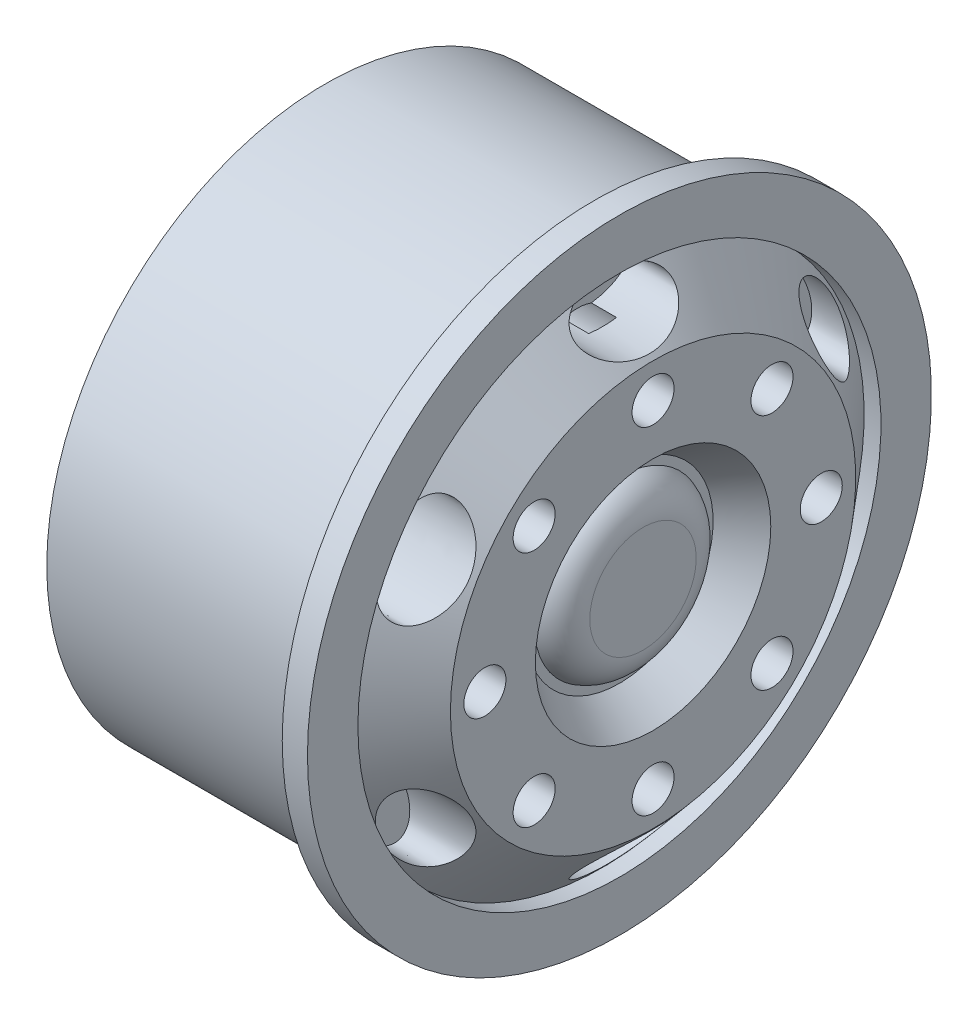
SolidWorks part; units mm, degrees
ref_plane "Front Plane" through (0, 0, 0) normal (0, 0, 1) x (1, 0, 0)
ref_plane "Top Plane" through (0, 0, 0) normal (0, 1, 0) x (1, 0, 0)
ref_plane "Right Plane" through (0, 0, 0) normal (1, 0, 0) x (0, 0, -1)
sketch "Sketch1" plane through (0, 0, 0) normal (0, 1, 0) x (1, 0, 0)
  line L0 (-37.2789, 0) -> (44.8184, 0) construction
  line L7 (12.1398, 7) -> (12.1398, 12.05)
  line L12 (-7.3602, 14.55) -> (-7.3602, 16.55)
  line L13 (-7.3602, 16.55) -> (8.6398, 16.55)
  line L14 (10.1398, 16.55) -> (10.1398, 15.55)
  line L15 (10.1398, 16.55) -> (10.1398, 18.55)
  line L16 (10.1398, 18.55) -> (8.6398, 18.55)
  line L17 (8.6398, 18.55) -> (8.6398, 16.55)
  line L18 (10.1398, 15.55) -> (9.1398, 15.55)
  line L23 (9.1398, 15.55) -> (12.1398, 12.05)
  line L25 (-7.3602, 14.55) -> (-7.3602, 0)
  line L34 (-7.3602, 0) -> (11.5416, 0)
  line L35 (12.1398, 7) -> (10.1398, 5.5718)
  line L36 (10.1398, 5.5718) -> (10.1398, 5.0718)
  line L37 (10.1398, 5.0718) -> (11.5416, 5.0718)
  line L38 (11.5416, 5.0718) -> (11.5416, 0)
  point P4 (7.9363, 16.8502)
  point P5 (4.0798, 13.7427)
  point P16 (8.0798, 11.847)
  dimension "D1" = 29.1
  dimension "D2" = 10.1436
  dimension "D4" = 2
  dimension "D5" = 3.5
  dimension "D6" = 17.5
  dimension "D7" = 1.5
  dimension "D8" = 2
  dimension "D9" = 1
  dimension "D10" = 1
  dimension "D11" = 2
  dimension "D12" = 33.1
  dimension "D3" = 0.5
  dimension "D13" = 2
revolve "Revolve1" add sketch "Sketch1" angle 360 about L0
sketch "Sketch2" plane through (12.1398, 0, 0) normal (1, 0, 0) x (0, 0, -1)
  line L0 (0, 12.05) -> (0, -12.05) construction
  line L1 (-12.05, 0) -> (12.05, 0) construction
  circle A0 centre (0, 0) radius 12.05 construction
  circle A1 centre (0, 0) radius 10 construction
  circle A2 centre (0, 10) radius 1.25
  circle A3 centre (7.0711, 7.0711) radius 1.25
  circle A4 centre (10, 0) radius 1.25
  circle A5 centre (7.0711, -7.0711) radius 1.25
  circle A6 centre (0, -10) radius 1.25
  circle A7 centre (-7.0711, -7.0711) radius 1.25
  circle A8 centre (-10, 0) radius 1.25
  circle A9 centre (-7.0711, 7.0711) radius 1.25
  circle A12 centre (0, 0) radius 14 construction
  point P28 (0, 0)
  point P46 (0, 0)
  dimension "D1" = 20
  dimension "D2" = 2.5
  dimension "D4" = 28
  dimension "D3" = 8
extrude "Cut-Extrude1" cut sketch "Sketch2" against normal through all
sketch "Sketch3" plane through (-7.3602, 0, 0) normal (-1, 0, 0) x (0, 0, 1)
  circle A0 centre (0, 0) radius 10 construction
  circle A1 centre (0, 10) radius 2.5
  circle A2 centre (7.0711, 7.0711) radius 2.5
  circle A3 centre (10, 0) radius 2.5
  circle A4 centre (7.0711, -7.0711) radius 2.5
  circle A5 centre (0, -10) radius 2.5
  circle A6 centre (-7.0711, -7.0711) radius 2.5
  circle A7 centre (-10, 0) radius 2.5
  circle A8 centre (-7.0711, 7.0711) radius 2.5
  point P22 (0, 0)
  dimension "D1" = 20
  dimension "D2" = 5
  dimension "D3" = 8
extrude "Cut-Extrude2" cut sketch "Sketch3" against normal offset from surface (16.5 mm away) 3 up to face at (12.1398, 10, -1.25)
sketch "Sketch7" plane through (-7.3602, 0, 0) normal (-1, 0, 0) x (0, 0, 1)
  circle A0 centre (0, 0) radius 4.725
  dimension "D1" = 9.45
extrude "Cut-Extrude7" cut sketch "Sketch7" against normal blind 10
fillet "Fillet1" radius 2 1 edges at (11.5416, 0, 5.0718)
sketch "Sketch8" plane through (10.1398, 0, 0) normal (1, 0, 0) x (0, 0, -1)
  circle A0 centre (0, 0) radius 13.8 construction
  ellipse E0 centre (0, 13.8) end of major axis (3, 13.8) minor radius 1.5
  ellipse E1 centre (11.9512, 6.9) end of major axis (10.4512, 9.4981) minor radius 1.5
  ellipse E2 centre (11.9512, -6.9) end of major axis (10.4512, -9.4981) minor radius 1.5
  ellipse E3 centre (0, -13.8) end of major axis (-3, -13.8) minor radius 1.5
  ellipse E4 centre (-11.9512, -6.9) end of major axis (-13.4512, -4.3019) minor radius 1.5
  ellipse E5 centre (-11.9512, 6.9) end of major axis (-13.4512, 4.3019) minor radius 1.5
  point P42 (0, 0)
  dimension "D1" = 27.6
  dimension "D2" = 6
  dimension "D3" = 3
  dimension "D4" = 6
extrude "Cut-Extrude8" cut sketch "Sketch8" against normal mid plane 5
sketch "Sketch4" plane through (13.1398, 0, 0) normal (1, 0, 0) x (0, 0, -1)
  circle A0 centre (0, 0) radius 13.75 construction
  circle A1 centre (0, 13.75) radius 1.25
  dimension "D1" = 2.5
  dimension "D2" = 27.5
extrude "Cut-Extrude5" cut sketch "Sketch4" against normal blind 5
